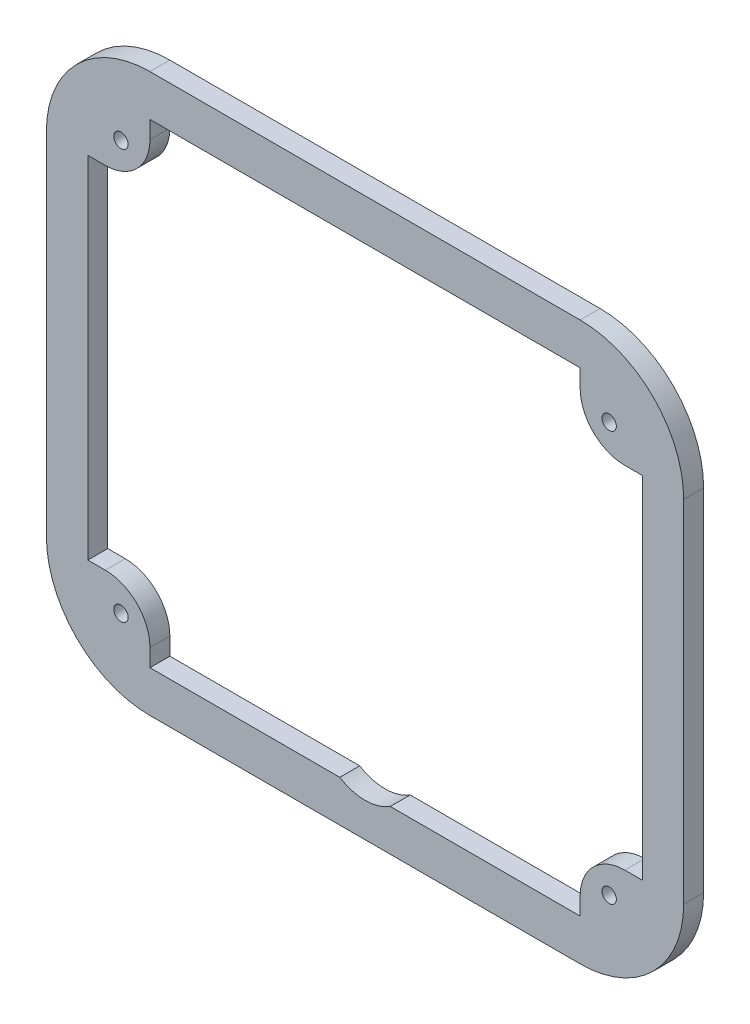
SolidWorks part; units mm, degrees
material "Delrin"
ref_plane "Front Plane" through (0, 0, 0) normal (0, 0, 1) x (1, 0, 0)
ref_plane "Top Plane" through (0, 0, 0) normal (0, 1, 0) x (1, 0, 0)
ref_plane "Right Plane" through (0, 0, 0) normal (1, 0, 0) x (0, 0, -1)
sketch "Sketch1" plane through (0, 0, 0) normal (0, 0, 1) x (1, 0, 0)
  line L0 (-17.145, -18.923) -> (-2.0127, -18.923)
  line L1 (17.145, 22.225) -> (-17.145, 22.225)
  line L2 (25.4, 13.97) -> (25.4, -13.97)
  line L3 (17.145, -22.225) -> (-17.145, -22.225)
  line L4 (-25.4, 13.97) -> (-25.4, -13.97)
  line L5 (25.4, 22.225) -> (-25.4, -22.225) construction
  line L6 (25.4, -22.225) -> (-25.4, 22.225) construction
  line L7 (2.0127, -18.923) -> (17.145, -18.923)
  line L9 (-22.098, 13.97) -> (-17.145, 13.97)
  line L10 (-22.098, 13.97) -> (-22.098, -13.97)
  line L12 (17.145, 18.923) -> (17.145, 13.97)
  line L13 (22.098, 13.97) -> (22.098, -13.97)
  line L14 (17.145, 18.923) -> (-17.145, 18.923)
  line L15 (-17.145, 13.97) -> (-17.145, 18.923)
  line L16 (17.145, 13.97) -> (22.098, 13.97)
  line L17 (0, 0) -> (-26.9405, 22.6057) construction
  line L18 (0, 18.415) -> (0, -18.415) construction
  line L19 (-1007.9925, 0) -> (48992.0075, 0) construction
  line L20 (-17.145, -18.923) -> (-17.145, -13.97)
  line L21 (-17.145, -13.97) -> (-22.098, -13.97)
  line L22 (17.145, -18.923) -> (17.145, -13.97)
  line L23 (17.145, -13.97) -> (22.098, -13.97)
  line L36 (17.145, -18.923) -> (-17.145, -18.923) construction
  arc A0 (-2.0127, -18.923) -> (2.0127, -18.923) centre (0, -15.748) ccw
  arc A1 (-17.145, 22.225) -> (-25.4, 13.97) centre (-17.145, 13.97) ccw
  arc A2 (17.145, 22.225) -> (25.4, 13.97) centre (17.145, 13.97) cw
  arc A3 (25.4, -13.97) -> (17.145, -22.225) centre (17.145, -13.97) cw
  arc A4 (-17.145, -22.225) -> (-25.4, -13.97) centre (-17.145, -13.97) cw
  arc A7 (17.145, 18.923) -> (22.098, 13.97) centre (17.145, 13.97) cw construction
  arc A8 (-17.145, 18.923) -> (-22.098, 13.97) centre (-17.145, 13.97) ccw construction
  circle A9 centre (-19.4575, 16.3268) radius 0.5715
  circle A10 centre (19.4575, 16.3268) radius 0.5715
  circle A11 centre (19.4575, -16.3268) radius 0.5715
  circle A12 centre (-19.4575, -16.3268) radius 0.5715
  arc A13 (-17.145, -18.923) -> (-22.098, -13.97) centre (-17.145, -13.97) cw construction
  arc A14 (22.098, -13.97) -> (17.145, -18.923) centre (17.145, -13.97) cw construction
  point P0 (0, 0)
  dimension "D4" = 7.5184
  dimension "D6" = 8.255
  dimension "D7" = 8.255
  dimension "D8" = 8.255
  dimension "D9" = 8.255
  dimension "D5" = 1.143
  dimension "D1" = 50.8
  dimension "D2" = 44.45
  dimension "D10" = 3.302
  dimension "D3" = 3.175
  dimension "D11" = 25.4
  dimension "D13" = 40
extrude "Boss-Extrude1" add sketch "Sketch1" along normal blind 1.5875
fillet "Fillet1" radius 3.556 4 edges at (17.145, -13.97, 0.7937) (17.145, 13.97, 0.7937) (-17.145, -13.97, 0.7937) (-17.145, 13.97, 0.7937)
